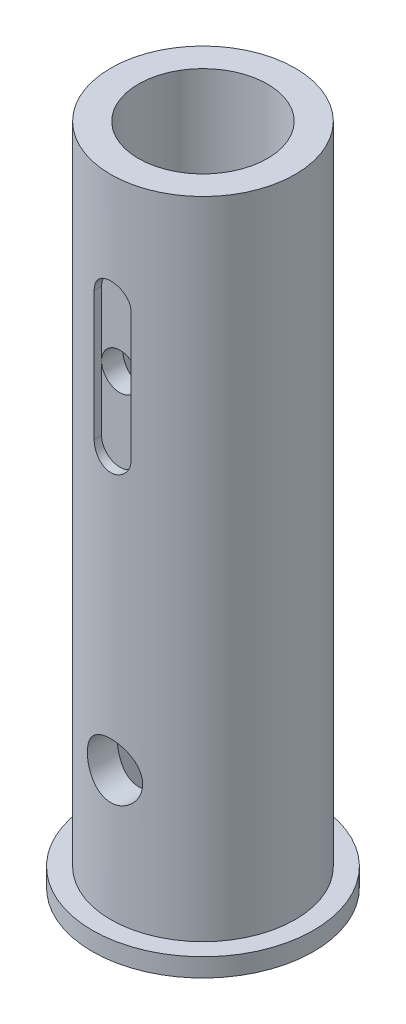
SolidWorks part; units mm, degrees
ref_plane "Front Plane" through (0, 0, 0) normal (0, 0, 1) x (1, 0, 0)
ref_plane "Top Plane" through (0, 0, 0) normal (0, 1, 0) x (1, 0, 0)
ref_plane "Right Plane" through (0, 0, 0) normal (1, 0, 0) x (0, 0, -1)
sketch "Sketch2" plane through (0, 0, 0) normal (0, 1, 0) x (1, 0, 0)
  circle A0 centre (0, 0) radius 12
  circle A1 centre (0, 0) radius 10
  dimension "D1" = 24
  dimension "D2" = 20
extrude "Boss-Extrude1" add sketch "Sketch2" against normal blind 2
extrude "Boss-Extrude2" add sketch "Sketch2<2>" along normal blind 70 and the other way up to surface (2 mm away) contours A1 region at (0, 0, 0) other way up to face at (0, -2, 10)
sketch "Sketch2<2>" plane through (0, 0, 0) normal (0, 1, 0) x (1, 0, 0) same geometry as "Sketch2"
sketch "Sketch3" plane through (0, 70, 0) normal (0, 1, 0) x (1, 0, 0)
  circle A0 centre (0, 0) radius 7
  dimension "D1" = 14
extrude "Cut-Extrude1" cut sketch "Sketch3" against normal through all contours A0
sketch "Sketch4" plane through (0, 0, 0) normal (0, 0, 1) x (1, 0, 0)
  line L0 (0, 44) -> (0, 58) construction
  line L1 (-2, 44) -> (-2, 58)
  line L2 (2, 44) -> (2, 58)
  line L3 (7, 70) -> (-7, 70) construction
  line L4 (10, 70) -> (-10, 70) construction
  arc A0 (-2, 44) -> (2, 44) centre (0, 44) ccw
  arc A1 (2, 58) -> (-2, 58) centre (0, 58) ccw
  circle A2 centre (0, 51) radius 2
  circle A3 centre (0, 14) radius 3
  point P3 (0, 51)
  dimension "D1" = 2
  dimension "D4" = 6
  dimension "D2" = 14
  dimension "D3" = 19
  dimension "D5" = 56
extrude "Cut-Extrude2" cut sketch "Sketch4" along normal through all contours A3 region at (0, 14, 0)
extrude "Cut-Extrude3" cut sketch "Sketch4<4>" along normal through all contours A2
sketch "Sketch4<4>" plane through (0, 0, 0) normal (0, 0, 1) x (1, 0, 0) same geometry as "Sketch4"
extrude "Cut-Extrude4" cut sketch "Sketch4<6>" along normal through all contours A1 L1 A0 L2
sketch "Sketch4<6>" plane through (0, 0, 0) normal (0, 0, 1) x (1, 0, 0) same geometry as "Sketch4"
extrude "Boss-Extrude3" add sketch "Sketch4<7>" along normal blind 9 contours A2 L2 A1 L1 | L2 A1 L1 A0 region at (0, 56.0708, 0)
sketch "Sketch4<7>" plane through (0, 0, 0) normal (0, 0, 1) x (1, 0, 0) same geometry as "Sketch4"
sketch "Sketch5" plane through (0, 70, 0) normal (0, 1, 0) x (1, 0, 0)
  line L0 (3.0117, -6.319) -> (3.9447, 2.0182)
  line L1 (3.9447, 2.0182) -> (-3.1374, 2.2384)
  line L2 (-3.1374, 2.2384) -> (-2.6737, -6.4693)
  arc A0 (-2.6737, -6.4693) -> (3.0117, -6.319) centre (0, 0) ccw
  circle A1 centre (0, 0) radius 7 construction
extrude "Cut-Extrude5" cut sketch "Sketch5" against normal through all
sketch "Sketch6" plane through (0, 0, 9) normal (0, 0, 1) x (1, 0, 0)
  line L2 (-2, 58) -> (-2, 44)
  line L3 (2, 44) -> (2, 58)
  line L4 (-2, 58) -> (-2, 44)
  line L5 (2, 44) -> (2, 58)
  circle A0 centre (0, 51) radius 2
  arc A3 (-2, 44) -> (2, 44) centre (0, 44) ccw
  arc A4 (2, 58) -> (-2, 58) centre (0, 58) ccw
  arc A5 (-2, 44) -> (2, 44) centre (0, 44) ccw
  arc A6 (2, 58) -> (-2, 58) centre (0, 58) ccw
  point P2 (0, 0)
  point P5 (0, 0)
  point P10 (-2, 51)
  dimension "D1" = 0
extrude "Cut-Extrude6" cut sketch "Sketch6" against normal blind 9 contours A0
